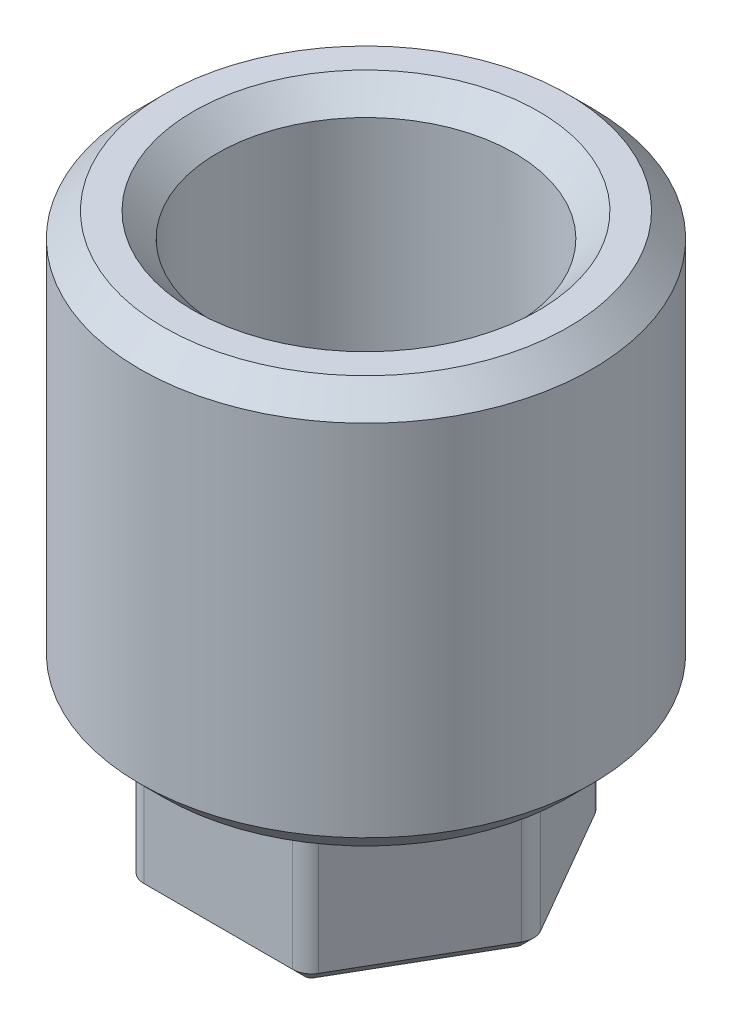
SolidWorks part; units mm, degrees
ref_plane "Front" through (0, 0, 0) normal (0, 0, 1) x (1, 0, 0)
ref_plane "Top" through (0, 0, 0) normal (0, 1, 0) x (1, 0, 0)
ref_plane "Right" through (0, 0, 0) normal (1, 0, 0) x (0, 0, -1)
sketch "Sketch1" plane through (0, 0, 0) normal (0, 1, 0) x (1, 0, 0)
  line L1 (1.7964, 3.1115) -> (-1.7964, 3.1115)
  line L2 (-1.7964, 3.1115) -> (-3.5929, 0)
  line L3 (-3.5929, 0) -> (-1.7964, -3.1115)
  line L4 (-1.7964, -3.1115) -> (1.7964, -3.1115)
  line L5 (1.7964, -3.1115) -> (3.5929, 0)
  line L6 (3.5929, 0) -> (1.7964, 3.1115)
  circle A0 centre (0, 0) radius 3.1115 construction
  dimension "D1" = 6.223
extrude "Boss-Extrude1" add sketch "Sketch1" along normal blind 3.175
sketch "Sketch2" plane through (0, 3.175, 0) normal (0, 1, 0) x (1, 0, 0)
  circle A0 centre (0, 0) radius 4.7625
  dimension "D1" = 9.525
extrude "Boss-Extrude2" add sketch "Sketch2" along normal blind 2.2301
sketch "Sketch3" plane through (0, 5.4051, 0) normal (0, 1, 0) x (1, 0, 0)
  circle A0 centre (0, 0) radius 3.127
  circle A1 centre (0, 0) radius 4.7625 construction
  circle A2 centre (0, 0) radius 4.7625
  dimension "D1" = 6.254
extrude "Boss-Extrude3" add sketch "Sketch3" along normal blind 6.35
sketch "Sketch4" plane through (0, 5.4051, 0) normal (0, 1, 0) x (1, 0, 0)
  line L0 (-3.0944, 0.45) -> (3.0944, 0.45)
  line L1 (-3.0944, -0.45) -> (3.0944, -0.45)
  line L2 (0, -0.45) -> (0, 0.45) construction
  circle A0 centre (0, 0) radius 3.127 construction
  arc A1 (3.0944, -0.45) -> (3.0944, 0.45) centre (0, 0) ccw
  arc A2 (-3.0944, 0.45) -> (-3.0944, -0.45) centre (0, 0) ccw
  dimension "D1" = 0.9
extrude "Boss-Extrude4" add sketch "Sketch4" along normal blind 1.5
sketch "Sketch5" plane through (0, 0, 0) normal (0, -1, 0) x (1, 0, 0)
  circle A0 centre (0, 0) radius 1.5875
  dimension "D1" = 3.175
extrude "Cut-Extrude1" [suppressed] cut sketch "Sketch5" against normal blind 0.889
fillet "Fillet1-1/64" radius 0.3969 20 edges at (1.7964, 1.5875, 3.1115) (-1.7964, 1.5875, 3.1115) (-3.5929, 1.5875, 0) (-1.7964, 1.5875, -3.1115) (3.5929, 1.5875, 0) (1.7964, 1.5875, -3.1115) (0, 3.175, 3.1115) (-2.6946, 3.175, 1.5558) (-2.6946, 3.175, -1.5557) (2.6946, 3.175, -1.5557) (2.6946, 3.175, 1.5557) (0, 3.175, -3.1115) (-3.0944, 6.1551, -0.45) (-3.0944, 6.1551, 0.45) (0, 5.4051, -0.45) (0, 5.4051, -3.127) (3.0944, 6.1551, -0.45) (0, 5.4051, 0.45) (3.0944, 6.1551, 0.45) (0, 5.4051, 3.127)
fillet "Fillet2-1/128" [suppressed] radius 0.1984
chamfer "Chamfer1-0.02" distance 0.508 angle 45 3 edges at (0, 11.7551, 3.127) (0, 11.7551, 4.7625) (0, 3.175, 4.7625)
chamfer "Chamfer2-0.005" distance 0.127 angle 45 6 edges at (-2.9167, 6.9051, 0.6138) (2.9167, 6.9051, 0.6138) (0, 6.9051, 0.45) (2.9167, 6.9051, -0.6138) (-2.9167, 6.9051, -0.6138) (0, 6.9051, -0.45)
chamfer "Chamfer3-0.01" distance 0.254 angle 45 12 edges at (3.5315, 0, 0) (2.6946, 0, -1.5557) (1.7657, 0, -3.0583) (0, 0, -3.1115) (-1.7657, 0, -3.0583) (-2.6946, 0, -1.5557) (-3.5315, 0, 0) (-2.6946, 0, 1.5558) (-1.7657, 0, 3.0583) (0, 0, 3.1115) (1.7657, 0, 3.0583) (2.6946, 0, 1.5557)
